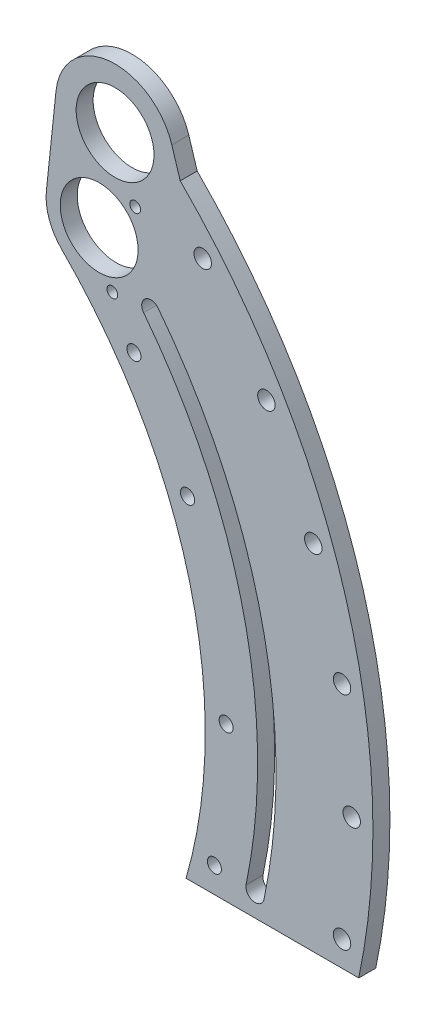
SolidWorks part; units mm, degrees
material "6061-T6 (SS)"
ref_plane "Front Plane" through (0, 0, 0) normal (0, 0, 1) x (1, 0, 0)
ref_plane "Top Plane" through (0, 0, 0) normal (0, 1, 0) x (1, 0, 0)
ref_plane "Right Plane" through (0, 0, 0) normal (1, 0, 0) x (0, 0, -1)
sketch "Sketch1" plane through (0, 0, 0) normal (0, 0, 1) x (1, 0, 0)
  line L0 (0, 0) -> (177.8, 0) construction
  line L1 (177.8, 0) -> (183.3563, 0) construction
  line L2 (0, 0) -> (191.1772, 6.6761) construction
  line L3 (0, 0) -> (182.7798, 182.7798) construction
  line L4 (184.7031, 10.1184) -> (184.959, 2.7905) construction
  line L5 (184.959, 2.7905) -> (191.4331, -0.6518) construction
  line L6 (191.4331, -0.6518) -> (197.6513, 3.2337) construction
  line L7 (197.6513, 3.2337) -> (197.3954, 10.5616) construction
  line L8 (197.3954, 10.5616) -> (190.9213, 14.0039) construction
  line L9 (190.9213, 14.0039) -> (184.7031, 10.1184) construction
  line L10 (156.6987, 109.7216) -> (0, 0) construction
  line L11 (0, 0) -> (176.7324, 73.2049) construction
  line L12 (183.3563, 0) -> (183.3563, -50.8) construction
  line L13 (176.1785, -50.8) -> (183.3563, -50.8) construction
  line L14 (0, 0) -> (186.7878, -41.275) construction
  line L15 (0, 0) -> (203.2, 0) construction
  line L16 (203.2, 0) -> (209.55, 0) construction
  line L17 (209.55, 0) -> (228.6, 0) construction
  line L18 (228.6, 0) -> (238.125, 0) construction
  line L19 (0, 0) -> (238.125, 0) construction
  line L20 (0, 0) -> (234.5073, 41.35) construction
  line L21 (176.1785, -50.8) -> (240.7615, -50.8)
  line L22 (0, 0) -> (238.125, 0) construction
  line L23 (0, 0) -> (234.5073, -41.35) construction
  line L24 (129.6524, 129.6524) -> (173.9925, 173.9925)
  line L25 (165.5338, 128.4903) -> (160.5177, 124.5966) construction
  line L26 (198.8628, -41.7593) -> (205.1195, -42.8625) construction
  arc A0 (183.3563, 0) -> (129.6524, 129.6524) centre (0, 0) ccw
  arc A1 (184.9438, 0) -> (130.775, 130.775) centre (0, 0) ccw construction
  circle A3 centre (191.1772, 6.6761) radius 6.35 construction
  circle A4 centre (191.1772, 6.6761) radius 2.6289
  circle A5 centre (156.6987, 109.7216) radius 2.6289
  circle A6 centre (176.7324, 73.2049) radius 2.667
  arc A7 (183.3563, 0) -> (176.1785, -50.8) centre (0, 0) cw
  circle A8 centre (186.7878, -41.275) radius 2.6289
  arc A9 (203.2, 0) -> (143.6841, 143.6841) centre (0, 0) ccw construction
  arc A10 (209.55, 0) -> (148.1742, 148.1742) centre (0, 0) ccw construction
  arc A11 (228.6, 0) -> (161.6446, 161.6446) centre (0, 0) ccw construction
  arc A12 (238.125, 0) -> (168.3798, 168.3798) centre (0, 0) ccw construction
  circle A13 centre (238.125, 0) radius 3.2639
  circle A14 centre (234.5073, 41.35) radius 3.2639
  circle A15 centre (223.7643, 81.4435) radius 3.2639
  circle A16 centre (206.2223, 119.0625) radius 3.2639
  circle A17 centre (182.4143, 153.0638) radius 3.2639
  arc A18 (240.7615, -50.8) -> (173.9925, 173.9925) centre (0, 0) ccw
  circle A19 centre (234.5073, -41.35) radius 3.2639
  arc A20 (209.55, 0) -> (165.5338, 128.4903) centre (0, 0) ccw construction
  arc A21 (160.5177, 124.5966) -> (203.2, 0) centre (0, 0) cw construction
  arc A22 (209.55, 0) -> (205.1195, -42.8625) centre (0, 0) cw construction
  arc A23 (203.2, 0) -> (198.8628, -41.7593) centre (0, 0) cw construction
  arc A24 (165.5338, 128.4903) -> (160.5177, 124.5966) centre (163.0257, 126.5435) ccw construction
  arc A25 (205.1195, -42.8625) -> (198.8628, -41.7593) centre (201.9911, -42.3109) cw construction
  arc A26 (202.946, 0) -> (198.6134, -41.711) centre (0, 0) cw
  arc A27 (205.3689, -42.9106) -> (198.6134, -41.711) centre (201.9911, -42.3109) cw
  arc A28 (209.804, 0) -> (205.3689, -42.9106) centre (0, 0) cw
  arc A29 (209.804, 0) -> (165.7345, 128.646) centre (0, 0) ccw
  arc A30 (165.7345, 128.646) -> (160.317, 124.4409) centre (163.0257, 126.5435) ccw
  arc A31 (160.317, 124.4409) -> (202.946, 0) centre (0, 0) cw
  point P9 (151.4971, 106.0794)
  point P20 (170.8657, 70.7749)
  point P27 (179.0372, -39.5623)
  dimension "D3" = 1.5875
  dimension "D4" = 12.7
  dimension "D6" = 5.2578
  dimension "D8" = 5.2578
  dimension "D12" = 5.334
  dimension "D14" = 50.8
  dimension "D15" = 5.2578
  dimension "D19" = 6.35
  dimension "D20" = 19.05
  dimension "D22" = 6.5278
  dimension "D26" = 7.9375
  dimension "D30" = 25.4
  dimension "D31" = 7.9375
  dimension "D33" = 183.3562
  dimension "D1" = 177.8
  dimension "D2" = 5.5562
  dimension "D5" = 2
  dimension "D7" = 45
  dimension "D9" = 6.35
  dimension "D10" = 10
  dimension "D11" = 22.5
  dimension "D13" = 6.35
  dimension "D16" = 9.525
  dimension "D17" = 7.9375
  dimension "D18" = 203.2
  dimension "D21" = 9.525
  dimension "D24" = 10
  dimension "D25" = 238.125
  dimension "D28" = 10
  dimension "D29" = 238.125
  dimension "D32" = 0.254
  dimension "D23" = 5
  dimension "D27" = 2
extrude "Boss-Extrude1" add sketch "Sketch1" along normal blind 6.35 contours L21 A18 L24 A0 A7 A19 A4 A5 A6 A8 A13 A14 A15 A16 A17 A22 A25 A23 A21 A24 A20 region at (184.0595, -26.0065, 0)
sketch "Sketch2" plane through (0, 0, 6.35) normal (0, 0, 1) x (1, 0, 0)
  line L0 (0, 0) -> (125.7236, 125.7236) construction
  line L1 (0, 0) -> (183.3562, 0) construction
  line L2 (125.7236, 125.7236) -> (143.6841, 143.6841) construction
  line L3 (129.6524, 129.6524) -> (173.9925, 173.9925) construction
  line L4 (143.6841, 143.6841) -> (149.6385, 177.4532) construction
  line L5 (129.6524, 129.6524) -> (173.9925, 173.9925) construction
  arc A0 (176.1785, -50.8) -> (129.6524, 129.6524) centre (0, 0) ccw construction
  circle A1 centre (143.6841, 143.6841) radius 14.5542
  circle A2 centre (143.6841, 143.6841) radius 25.4 construction
  circle A3 centre (143.6841, 143.6841) radius 11.43 construction
  circle A4 centre (143.6841, 143.6841) radius 19.05 construction
  circle A5 centre (149.6385, 177.4532) radius 22.86 construction
  circle A6 centre (149.6385, 177.4532) radius 14.5542
  dimension "D4" = 29.1084
  dimension "D5" = 50.8
  dimension "D6" = 22.86
  dimension "D7" = 38.1
  dimension "D8" = 45.72
  dimension "D9" = 35
  dimension "D10" = 29.1084
  dimension "D1" = 177.8
  dimension "D2" = 45
  dimension "D3" = 25.4
sketch "Sketch3" plane through (0, 0, 6.35) normal (0, 0, 1) x (1, 0, 0)
  line L0 (129.6524, 129.6524) -> (173.9925, 173.9925) construction
  line L1 (129.6524, 129.6524) -> (161.6446, 161.6446)
  line L3 (170.8592, 184.0585) -> (173.9925, 173.9925)
  line L4 (123.9497, 145.7645) -> (127.536, 179.7832)
  line L5 (161.6446, 161.6446) -> (173.9925, 173.9925)
  arc A1 (129.6524, 129.6524) -> (123.9497, 145.7645) centre (143.6841, 143.6841) cw
  arc A2 (170.8592, 184.0585) -> (127.536, 179.7832) centre (149.6385, 177.4532) ccw
  circle A3 centre (149.6385, 177.4532) radius 14.5542
  dimension "D1" = 25.4
  dimension "D2" = 29.1084
  dimension "D3" = 22.225
extrude "Boss-Extrude2" add sketch "Sketch3" against normal blind 6.35
sketch "Sketch4" plane through (0, 0, 6.35) normal (0, 0, 1) x (1, 0, 0)
  line L0 (143.6841, 143.6841) -> (157.1545, 157.1545) construction
  line L1 (125.7236, 125.7236) -> (143.6841, 143.6841) construction
  line L2 (143.6841, 143.6841) -> (148.6146, 125.2832) construction
  circle A0 centre (143.6841, 143.6841) radius 14.5542
  circle A1 centre (157.1545, 157.1545) radius 2.0193
  circle A2 centre (148.6146, 125.2832) radius 2.0193
  dimension "D1" = 29.1084
  dimension "D2" = 4.0386
  dimension "D4" = 4.0386
  dimension "D3" = 19.05
  dimension "D5" = 19.05
  dimension "D6" = 60
extrude "Cut-Extrude1" cut sketch "Sketch4" against normal through all
